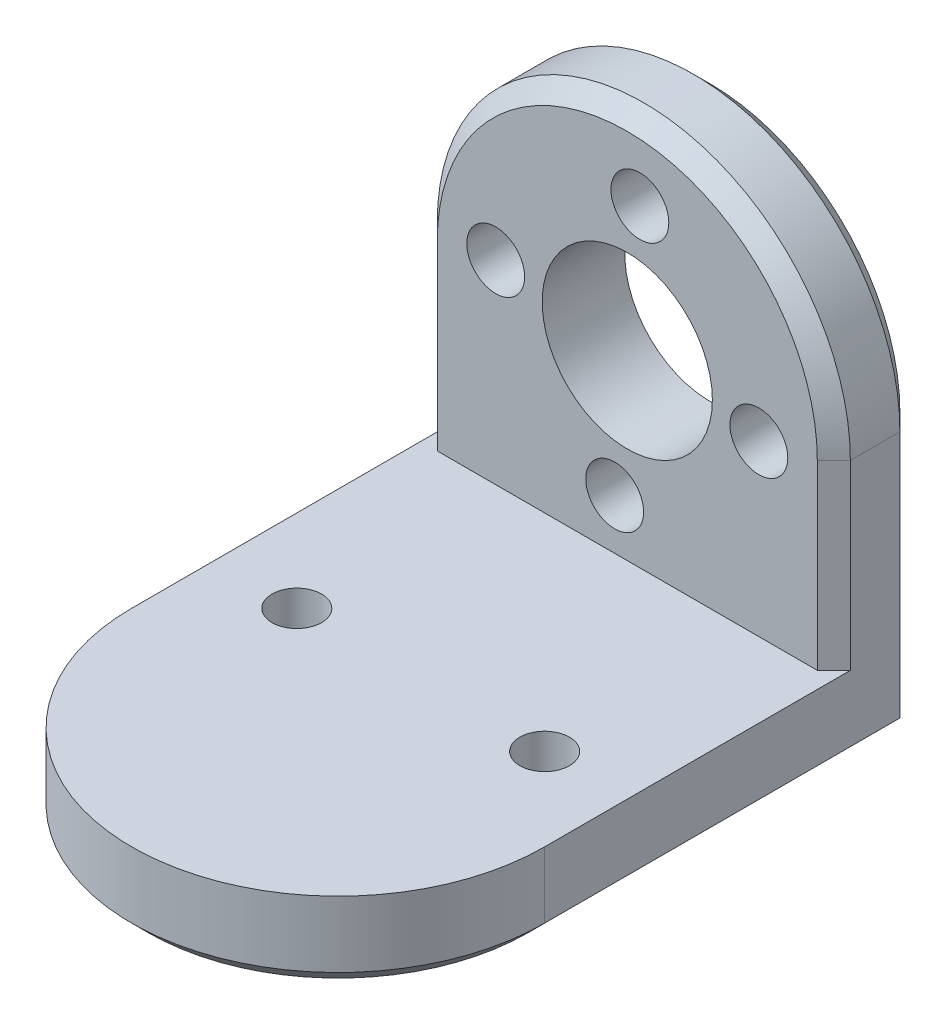
SolidWorks part; units mm, degrees
ref_plane "Plan de face" through (0, 0, 0) normal (0, 0, 1) x (1, 0, 0)
ref_plane "Plan de dessus" through (0, 0, 0) normal (0, 1, 0) x (1, 0, 0)
ref_plane "Plan de droite" through (0, 0, 0) normal (1, 0, 0) x (0, 0, -1)
sketch "Esquisse1" plane through (0, 0, 0) normal (0, 0, 1) x (1, 0, 0)
  line L0 (0, 5.15) -> (0, 12.5) construction
  circle A0 centre (0, 0) radius 5.15
  circle A1 centre (0, 0) radius 12.5
  dimension "D1" = 10.3
  dimension "D2" = 25
extrude "Boss.-Extru.1" add sketch "Esquisse1" along normal blind 5
sketch "Esquisse2" plane through (0, 0, 0) normal (0, 0, -1) x (-1, 0, 0)
  line L0 (-12.5, 0) -> (-12.5, -16)
  line L1 (0, 22.5651) -> (0, -23.047) construction
  line L2 (12.5, 0) -> (12.5, -16)
  line L3 (-12.5, -16) -> (12.5, -16)
  circle A0 centre (0, 0) radius 12.5 construction
  arc A1 (-12.5, 0) -> (12.5, 0) centre (0, 0) ccw
  dimension "D1" = 16
extrude "Boss.-Extru.2" add sketch "Esquisse2" against normal blind 5
sketch "Esquisse3" plane through (0, 0, 5) normal (0, 0, 1) x (1, 0, 0)
  line L0 (-12.5, -11) -> (12.5, -11)
  line L3 (-12.5, 0) -> (-12.5, -16)
  line L4 (-12.5, -16) -> (12.5, -16)
  line L5 (12.5, -16) -> (12.5, 0)
  line L6 (-12.5, -11) -> (-12.5, -16)
  line L7 (-12.5, -16) -> (12.5, -16)
  line L8 (12.5, -16) -> (12.5, -11)
  arc A1 (12.5, 0) -> (-12.5, 0) centre (0, 0) ccw
  dimension "D2" = 5
  dimension "D1" = 0
extrude "Boss.-Extru.3" add sketch "Esquisse3" along normal blind 30
sketch "Esquisse5" plane through (0, 0, 0) normal (0, 0, -1) x (-1, 0, 0)
  circle A0 centre (-0.7627, 7.9636) radius 1.75
  circle A1 centre (-7.9636, -0.7627) radius 1.75
  circle A2 centre (7.9636, 0.7627) radius 1.75
  circle A3 centre (0.7627, -7.9636) radius 1.75
extrude "Enlèv. mat.-Extru.1" cut sketch "Esquisse5" against normal through all
fillet "Congé1" 2 edges at (-12.5, -13.5, 35) (12.5, -13.5, 35) type full round first side face at (-12.5, -9, 13.3333) second side face at (12.5, -9, 13.3333) middle face at (0, -13.5, 35)
sketch "Esquisse6" plane through (0, -11, 0) normal (0, 1, 0) x (1, 0, 0)
  line L0 (0, 4.6489) -> (0, -4.6489) construction
  line L1 (-12.5, -22.5) -> (-12.5, -5) construction
  line L2 (12.5, -22.5) -> (12.5, -5) construction
  line L3 (-12.5, -17.5) -> (12.5, -17.5) construction
  circle A0 centre (-7.5, -17.5) radius 1.5
  circle A1 centre (7.5, -17.5) radius 1.5
  point P12 (0, 0)
  dimension "D3" = 3
  dimension "D1" = 17.5
  dimension "D2" = 5
extrude "Enlèv. mat.-Extru.2" cut sketch "Esquisse6" against normal through all contours A0 | A1
chamfer "Chanfrein1" distance 1 angle 45 3 edges at (12.5, -5.5, 5) (-12.5, -5.5, 5) (0, 12.5, 5)
chamfer "Chanfrein2" distance 1 angle 45 6 edges at (12.5, -8, 0) (0, 12.5, 0) (-12.5, -8, 0) (12.5, -16, 11.25) (-12.5, -16, 11.25) (0, -16, 35)
